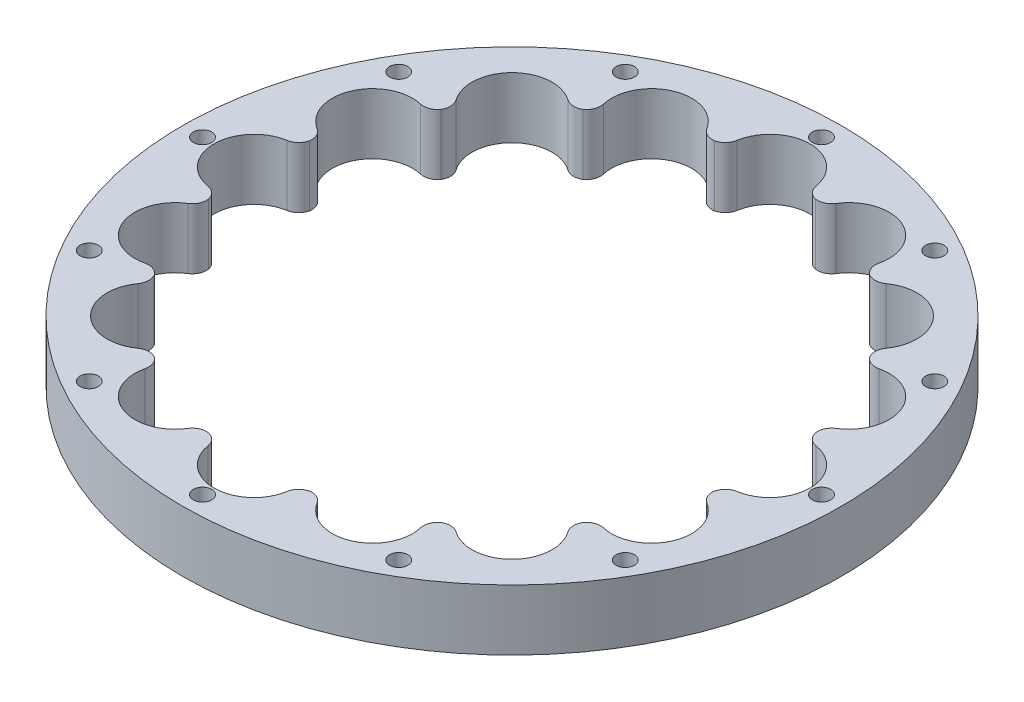
SolidWorks part; units mm, degrees
ref_plane "Front Plane" through (0, 0, 0) normal (0, 0, 1) x (1, 0, 0)
ref_plane "Top Plane" through (0, 0, 0) normal (0, 1, 0) x (1, 0, 0)
ref_plane "Right Plane" through (0, 0, 0) normal (1, 0, 0) x (0, 0, -1)
sketch "Sketch1" plane through (0, 0, 0) normal (0, 1, 0) x (1, 0, 0)
  circle A0 centre (0, 0) radius 45
  circle A1 centre (0, 45) radius 7
  circle A2 centre (17.2208, 41.5746) radius 7
  circle A3 centre (31.8198, 31.8198) radius 7
  circle A4 centre (41.5746, 17.2208) radius 7
  circle A5 centre (45, 0) radius 7
  circle A6 centre (41.5746, -17.2208) radius 7
  circle A7 centre (31.8198, -31.8198) radius 7
  circle A8 centre (17.2208, -41.5746) radius 7
  circle A9 centre (0, -45) radius 7
  circle A10 centre (-17.2208, -41.5746) radius 7
  circle A11 centre (-31.8198, -31.8198) radius 7
  circle A12 centre (0, 0) radius 57.5
  circle A13 centre (0, 0) radius 54 construction
  circle A14 centre (0, 54) radius 1.6
  circle A15 centre (27, 46.7654) radius 1.6
  circle A16 centre (46.7654, 27) radius 1.6
  circle A17 centre (54, 0) radius 1.6
  circle A18 centre (46.7654, -27) radius 1.6
  circle A19 centre (27, -46.7654) radius 1.6
  circle A20 centre (0, -54) radius 1.6
  circle A21 centre (-27, -46.7654) radius 1.6
  circle A22 centre (-46.7654, -27) radius 1.6
  circle A23 centre (-54, 0) radius 1.6
  circle A24 centre (-46.7654, 27) radius 1.6
  circle A25 centre (-27, 46.7654) radius 1.6
  circle A26 centre (-41.5746, -17.2208) radius 7
  circle A27 centre (-45, 0) radius 7
  circle A28 centre (-41.5746, 17.2208) radius 7
  circle A29 centre (-31.8198, 31.8198) radius 7
  circle A30 centre (-17.2208, 41.5746) radius 7
  point P27 (0, 0)
  point P54 (0, 0)
  dimension "D1" = 90
  dimension "D2" = 14
  dimension "D4" = 115
  dimension "D5" = 108
  dimension "D6" = 3.2
  dimension "D3" = 16
  dimension "D7" = 12
extrude "Boss-Extrude1" add sketch "Sketch1" along normal blind 10.6 contours A12 A25 A24 A23 A22 A21 A20 A19 A18 A17 A16 A15 A14 A11 A0 A1 A2 A3 A4 A5 A6 A7 A8 A9 A10 region at (-55.8737, 0, 0)
fillet "Fillet1" radius 2.5 32 edges at (38.4009, 5.3, -23.46) (36.3696, 5.3, -26.5001) (44.4556, 5.3, -6.9788) (43.7422, 5.3, -10.5648) (44.4556, 5.3, 6.9788) (43.7422, 5.3, 10.5648) (38.4009, 5.3, 23.46) (36.3696, 5.3, 26.5001) (26.5001, 5.3, 36.3696) (23.46, 5.3, 38.4009) (6.9788, 5.3, 44.4556) (10.5648, 5.3, 43.7422) (-6.9788, 5.3, 44.4556) (-10.5648, 5.3, 43.7422) (-23.46, 5.3, 38.4009) (-26.5001, 5.3, 36.3696) (26.5001, 5.3, -36.3696) (23.46, 5.3, -38.4009) (10.5648, 5.3, -43.7422) (6.9788, 5.3, -44.4556) (-6.9788, 5.3, -44.4556) (-36.3696, 5.3, 26.5001) (-10.5648, 5.3, -43.7422) (-23.46, 5.3, -38.4009) (-26.5001, 5.3, -36.3696) (-36.3696, 5.3, -26.5001) (-38.4009, 5.3, -23.46) (-43.7422, 5.3, -10.5648) (-44.4556, 5.3, -6.9788) (-44.4556, 5.3, 6.9788) (-43.7422, 5.3, 10.5648) (-38.4009, 5.3, 23.46)
